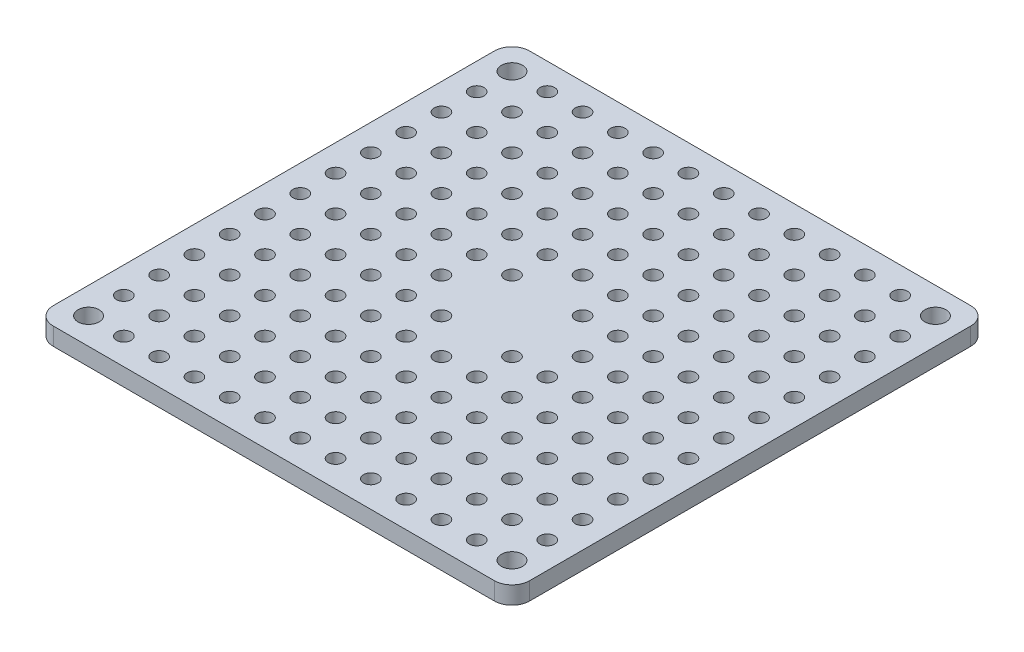
SolidWorks part; units mm, degrees
material "AISI 1020"
ref_plane "Front Plane" through (0, 0, 0) normal (0, 0, 1) x (1, 0, 0)
ref_plane "Top Plane" through (0, 0, 0) normal (0, 1, 0) x (1, 0, 0)
ref_plane "Right Plane" through (0, 0, 0) normal (1, 0, 0) x (0, 0, -1)
sketch "Sketch1" plane through (0, 0, 0) normal (0, 1, 0) x (1, 0, 0)
  line L1 (-135, 135) -> (135, 135)
  line L2 (-135, 135) -> (-135, -135)
  line L3 (-135, -135) -> (135, -135)
  line L4 (135, 135) -> (135, -135)
  line L5 (-135, 135) -> (135, -135) construction
  line L6 (-135, -135) -> (135, 135) construction
  point P0 (0, 0)
  dimension "D1" = 270
  dimension "D2" = 270
extrude "Boss-Extrude1" add sketch "Sketch1" along normal blind 10
sketch "Sketch3" plane through (0, 10, 0) normal (0, 1, 0) x (1, 0, 0)
  circle A110 centre (0, 0) radius 4
  circle A111 centre (20, 0) radius 4
  circle A112 centre (40, 0) radius 4
  circle A113 centre (60, 0) radius 4
  circle A114 centre (80, 0) radius 4
  circle A115 centre (100, 0) radius 4
  circle A116 centre (120, 0) radius 4
  dimension "D1" = 8
sketch "Sketch4" plane through (0, 10, 0) normal (0, 1, 0) x (1, 0, 0)
  line L0 (135, 135) -> (-135, 135) construction
  line L1 (-135, 135) -> (-75.8392, 135)
  line L2 (-135, 135) -> (-135, 85)
  line L3 (-95, 75) -> (-75.8392, 75)
  line L4 (-75.8392, 135) -> (-75.8392, 75)
  line L5 (135, 135) -> (75.8392, 135)
  line L6 (135, 135) -> (135, 85)
  line L7 (95, 75) -> (75.8392, 75)
  line L8 (75.8392, 135) -> (75.8392, 75)
  line L9 (-70.3392, 105) -> (69.6608, 105)
  line L10 (-70.3392, 105) -> (-70.3392, 135)
  line L11 (-70.3392, 135) -> (69.6608, 135)
  line L12 (69.6608, 105) -> (69.6608, 135)
  line L13 (-135, 135) -> (-135, -135) construction
  line L14 (-135, -105) -> (135, -105)
  line L15 (-135, -105) -> (-135, -135)
  line L16 (-135, -135) -> (135, -135)
  line L17 (135, -105) -> (135, -135)
  line L18 (135, -135) -> (135, 135) construction
  line L19 (74.1608, -80) -> (95, -80)
  line L20 (74.1608, -80) -> (74.1608, -100)
  line L21 (74.1608, -100) -> (135, -100)
  line L22 (135, -90) -> (135, -100)
  line L24 (-95, -80) -> (-75.8392, -80)
  line L25 (-135, -90) -> (-135, -100)
  line L26 (-135, -100) -> (-75.8392, -100)
  line L27 (-75.8392, -80) -> (-75.8392, -100)
  line L29 (135, 85) -> (135, -90)
  line L31 (95, 75) -> (95, -80)
  line L33 (-135, 85) -> (-135, -90)
  line L35 (-95, 75) -> (-95, -80)
  dimension "D1" = 60
  dimension "D2" = 60
  dimension "D3" = 140
  dimension "D4" = 5.5
  dimension "D5" = 60
  dimension "D6" = 60
  dimension "D7" = 30
  dimension "D8" = 30
  dimension "D9" = 20
  dimension "D10" = 20
  dimension "D11" = 5
  dimension "D12" = 5
  dimension "D13" = 150
  dimension "D14" = 60
  dimension "D15" = 40
  dimension "D16" = 40
extrude "Boss-Extrude2" add sketch "Sketch4" against normal blind 10
fillet "Fillet1" radius 10 4 edges at (-135, 5, 135) (135, 5, 135) (135, 5, -135) (-135, 5, -135)
hole_wizard "Ø8.3 (8.3) Diameter Hole1" positions "Sketch11" profile "Sketch12" hole size "Ø8.3" standard "ANSI Metric"
sketch "Sketch11" plane through (0, 10, 0) normal (0, 1, 0) x (1, 0, 0)
  point P0 (0, 0)
  point P3 (20, 0)
  point P6 (40, 0)
  point P9 (60, 0)
  point P12 (80, 0)
  point P15 (100, 0)
  point P18 (120, 0)
sketch "Sketch12" plane through (0, 10, 0) normal (1, 0, 0) x (0, 0, 1)
  line L0 (0, 0) -> (0, 22.2436)
  line L1 (0, 22.2436) -> (4.15, 19.75)
  line L2 (4.15, 19.75) -> (4.15, 0)
  line L5 (4.15, 0) -> (0, 0)
  line L10 (0, 22.2436) -> (-4.15, 19.75) construction
  line L11 (0, -6.35) -> (0, 107.95) construction
  dimension "Hole Dia." = 8.3
  dimension "Hole Depth" = 19.75
  dimension "Drill Angle" = 118
pattern_linear "LPattern1" count 7 spacing 20 along (0, 0, 1) of "Ø8.3 (8.3) Diameter Hole1"
mirror "Mirror1" about plane through (0, 0, 0) normal (1, 0, 0) of "LPattern1", "Ø8.3 (8.3) Diameter Hole1"
mirror "Mirror2" about plane through (0, 0, 0) normal (0, 0, 1) of "Mirror1", "LPattern1"
sketch "Sketch13" plane through (0, 10, 0) normal (0, 1, 0) x (1, 0, 0)
  line L0 (-7.5, -7.5) -> (-7.5, -25)
  line L1 (-7.5, 25) -> (7.5, 25)
  line L2 (-7.5, 25) -> (-7.5, 7.5)
  line L3 (-7.5, -25) -> (7.5, -25)
  line L4 (7.5, 25) -> (7.5, 7.5)
  line L5 (-7.5, 25) -> (7.5, -25) construction
  line L6 (-7.5, -25) -> (7.5, 25) construction
  line L7 (-25, 7.5) -> (-7.5, 7.5)
  line L8 (-25, 7.5) -> (-25, -7.5)
  line L9 (-25, -7.5) -> (-7.5, -7.5)
  line L10 (25, 7.5) -> (25, -7.5)
  line L11 (-25, 7.5) -> (25, -7.5) construction
  line L12 (-25, -7.5) -> (25, 7.5) construction
  line L13 (7.5, 7.5) -> (25, 7.5)
  line L14 (7.5, -7.5) -> (7.5, -25)
  line L15 (7.5, -7.5) -> (25, -7.5)
  point P0 (0, 0)
  point P7 (0, 0)
  dimension "D1" = 15
  dimension "D2" = 15
  dimension "D3" = 50
  dimension "D4" = 50
extrude "Boss-Extrude5" add sketch "Sketch13" against normal up to surface (10 mm away) up to face at (20, 0, -115.85)
sketch "Sketch14" plane through (0, 10, 0) normal (0, 1, 0) x (1, 0, 0)
  circle A0 centre (-120, 120) radius 6
  circle A1 centre (120, 120) radius 6
  circle A2 centre (120, -120) radius 6
  circle A3 centre (-120, -120) radius 6
  dimension "D1" = 12
extrude "Cut-Extrude1" cut sketch "Sketch14" against normal through all
